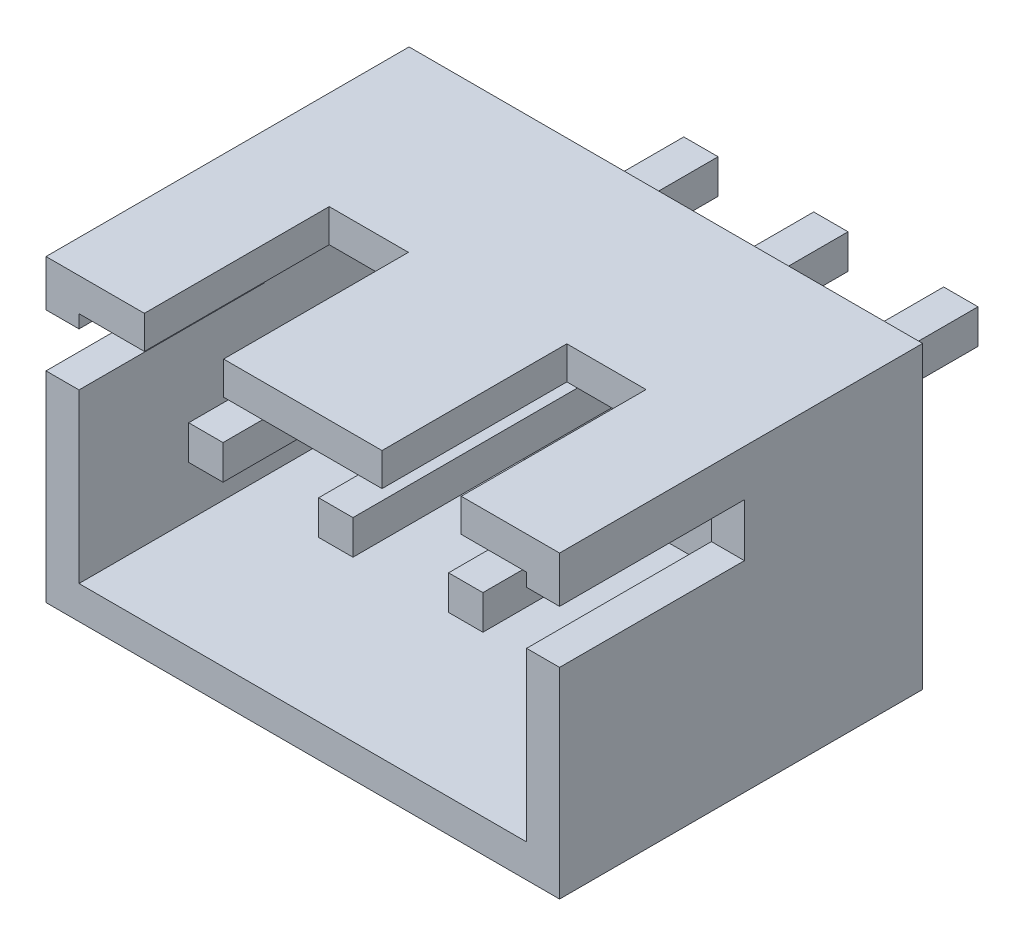
SolidWorks part; units mm, degrees
ref_plane "Front Plane" through (0, 0, 0) normal (0, 0, 1) x (1, 0, 0)
ref_plane "Top Plane" through (0, 0, 0) normal (0, 1, 0) x (1, 0, 0)
ref_plane "Right Plane" through (0, 0, 0) normal (1, 0, 0) x (0, 0, -1)
sketch "Sketch1" plane through (0, 0, 0) normal (0, 0, 1) x (1, 0, 0)
  line L1 (0, 0) -> (9.8806, 0)
  line L2 (0, 0) -> (0, 5.7658)
  line L3 (0, 5.7658) -> (9.8806, 5.7658)
  line L4 (9.8806, 0) -> (9.8806, 5.7658)
  dimension "D1" = 5.7658
  dimension "D2" = 9.8806
extrude "Boss-Extrude1" add sketch "Sketch1" along normal blind 6.985
sketch "Sketch2" plane through (0, 0, 0) normal (0, 0, -1) x (-1, 0, 0)
  line L0 (-7.4403, 3.4036) -> (-4.9403, 3.4036) construction
  line L1 (-4.9403, 3.4036) -> (-2.4403, 3.4036) construction
  line L2 (-4.9403, 3.4036) -> (-4.9403, 5.7658) construction
  line L3 (-9.8806, 5.7658) -> (0, 5.7658) construction
  line L5 (-7.7705, 3.0734) -> (-7.1101, 3.0734)
  line L6 (-7.7705, 3.0734) -> (-7.7705, 3.7338)
  line L7 (-7.7705, 3.7338) -> (-7.1101, 3.7338)
  line L8 (-7.1101, 3.0734) -> (-7.1101, 3.7338)
  line L9 (-7.7705, 3.0734) -> (-7.1101, 3.7338) construction
  line L10 (-7.7705, 3.7338) -> (-7.1101, 3.0734) construction
  line L11 (-4.6101, 3.0734) -> (-5.2705, 3.0734)
  line L12 (-4.6101, 3.0734) -> (-4.6101, 3.7338)
  line L13 (-4.6101, 3.7338) -> (-5.2705, 3.7338)
  line L14 (-5.2705, 3.0734) -> (-5.2705, 3.7338)
  line L15 (-4.6101, 3.0734) -> (-5.2705, 3.7338) construction
  line L16 (-4.6101, 3.7338) -> (-5.2705, 3.0734) construction
  line L17 (-2.1101, 3.0734) -> (-2.7705, 3.0734)
  line L18 (-2.1101, 3.0734) -> (-2.1101, 3.7338)
  line L19 (-2.1101, 3.7338) -> (-2.7705, 3.7338)
  line L20 (-2.7705, 3.0734) -> (-2.7705, 3.7338)
  line L21 (-2.1101, 3.0734) -> (-2.7705, 3.7338) construction
  line L22 (-2.1101, 3.7338) -> (-2.7705, 3.0734) construction
  circle A0 centre (-4.9403, 3.4036) radius 0.3302 construction
  circle A1 centre (-2.4403, 3.4036) radius 0.3302 construction
  circle A2 centre (-7.4403, 3.4036) radius 0.3302 construction
  dimension "D1" = 0.6604
  dimension "D2" = 2.5
  dimension "D3" = 2.6924
extrude "Boss-Extrude2" add sketch "Sketch2" along normal blind 3.175
sketch "Sketch4" plane through (0, 0, 6.985) normal (0, 0, 1) x (1, 0, 0)
  line L0 (9.8806, 0) -> (9.8806, 5.7658) construction
  line L1 (0.635, 5.1308) -> (9.2456, 5.1308)
  line L2 (0.635, 5.1308) -> (0.635, 0.635)
  line L3 (0.635, 0.635) -> (9.2456, 0.635)
  line L4 (9.2456, 5.1308) -> (9.2456, 0.635)
  line L5 (0, 0) -> (9.8806, 0) construction
  line L6 (0, 5.7658) -> (0, 0) construction
  line L7 (9.8806, 5.7658) -> (0, 5.7658) construction
  dimension "D1" = 0.635
  dimension "D2" = 0.635
  dimension "D3" = 0.635
  dimension "D4" = 0.635
extrude "Cut-Extrude1" cut sketch "Sketch4" against normal offset from surface (6.35 mm away) 0.635 up to face at (4.9403, 2.8829, 0)
extrude "Boss-Extrude3" add sketch "Sketch2<2>" against normal offset from surface (6.35 mm away) 0.635 up to face at (4.9403, 2.8829, 6.985)
sketch "Sketch2<2>" plane through (0, 0, 0) normal (0, 0, -1) x (-1, 0, 0) same geometry as "Sketch2"
sketch "Sketch5" plane through (0, 0, 6.985) normal (0, 0, 1) x (1, 0, 0)
  line L0 (0, 5.7658) -> (0, 0) construction
  line L1 (0, 4.8768) -> (0.635, 4.8768)
  line L2 (0, 4.8768) -> (0, 3.8608)
  line L3 (0, 3.8608) -> (0.635, 3.8608)
  line L4 (0.635, 4.8768) -> (0.635, 3.8608)
  line L5 (0.635, 5.1308) -> (0.635, 0.635) construction
  line L6 (9.2456, 0.635) -> (9.2456, 5.1308) construction
  line L7 (9.2456, 4.8768) -> (9.8806, 4.8768)
  line L8 (9.2456, 4.8768) -> (9.2456, 3.8608)
  line L9 (9.2456, 3.8608) -> (9.8806, 3.8608)
  line L10 (9.8806, 4.8768) -> (9.8806, 3.8608)
  line L11 (9.8806, 0) -> (9.8806, 5.7658) construction
  line L12 (9.8806, 5.7658) -> (0, 5.7658) construction
  line L13 (6.4643, 5.7658) -> (7.9883, 5.7658)
  line L14 (6.4643, 5.7658) -> (6.4643, 5.1308)
  line L15 (6.4643, 5.1308) -> (7.9883, 5.1308)
  line L16 (7.9883, 5.7658) -> (7.9883, 5.1308)
  line L17 (9.2456, 5.1308) -> (0.635, 5.1308) construction
  line L18 (9.2456, 5.1308) -> (0.635, 5.1308) construction
  line L19 (1.8923, 5.7658) -> (3.4163, 5.7658)
  line L20 (1.8923, 5.7658) -> (1.8923, 5.1308)
  line L21 (1.8923, 5.1308) -> (3.4163, 5.1308)
  line L22 (3.4163, 5.7658) -> (3.4163, 5.1308)
  line L23 (3.4163, 5.4483) -> (6.4643, 5.4483) construction
  line L24 (4.9403, 5.4483) -> (4.9403, 5.7658) construction
  dimension "D1" = 1.016
  dimension "D2" = 0.254
  dimension "D3" = 3.048
  dimension "D4" = 1.524
extrude "Cut-Extrude2" cut sketch "Sketch5" against normal blind 3.556
